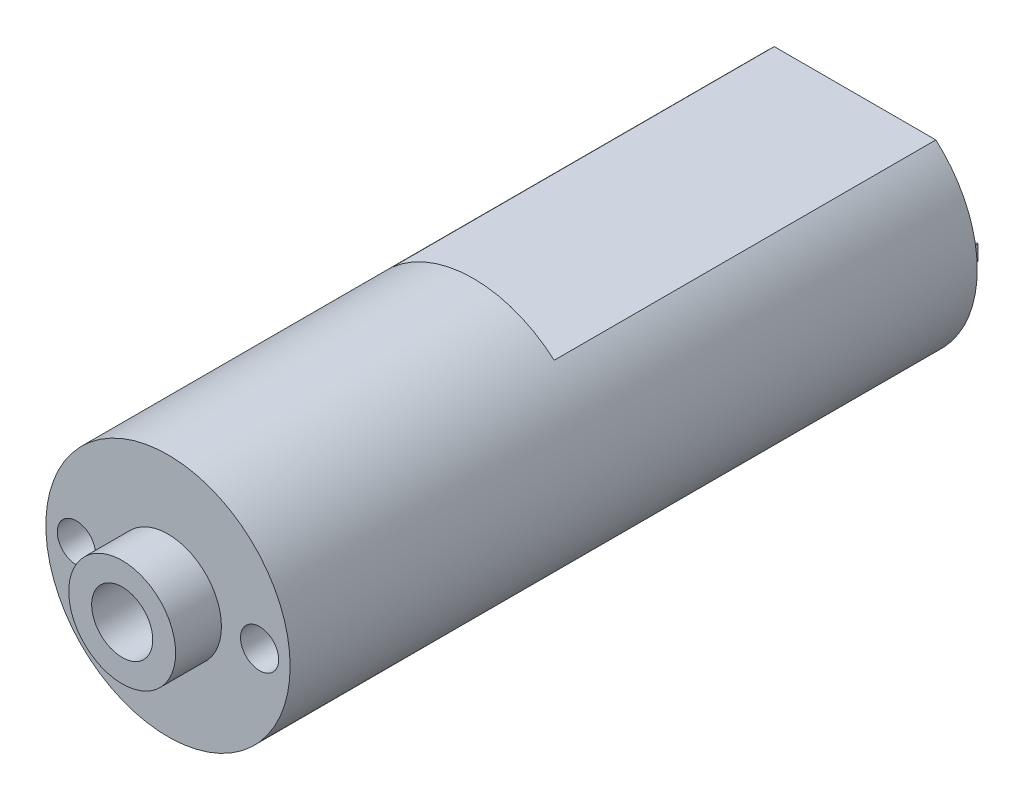
SolidWorks part; units mm, degrees
ref_plane "Ön Düzlem" through (0, 0, 0) normal (0, 0, 1) x (1, 0, 0)
ref_plane "Üst Düzlem" through (0, 0, 0) normal (0, 1, 0) x (1, 0, 0)
ref_plane "Sağ Düzlem" through (0, 0, 0) normal (1, 0, 0) x (0, 0, -1)
sketch "Sketch1" plane through (0, 0, 0) normal (0, 0, 1) x (1, 0, 0)
  line L0 (-6, 0) -> (6, 0) construction
  circle A0 centre (0, 0) radius 8
  circle A1 centre (0, 0) radius 2
  circle A2 centre (-6, 0) radius 1.25
  circle A3 centre (6, 0) radius 1.25
  circle A4 centre (0, 0) radius 3.5
  point P8 (0, 0)
  dimension "D1" = 16
  dimension "D2" = 4
  dimension "D4" = 2.5
  dimension "D5" = 7
  dimension "D3" = 12
extrude "Boss-Extrude1" add sketch "Sketch1" against normal blind 20 contours L0 A4 A1 | A4 L0 A1 | A0 A2 A4 A3 region at (0, 2.0783, 0) region at (2.75, -0.0783, 0) region at (-7.7737, 0, 0)
extrude "Boss-Extrude2" add sketch "Sketch1<3>" along normal blind 3 contours A4 L0 A1 | L0 A4 A1 region at (0, 2.0783, 0) region at (2.75, -0.0783, 0)
sketch "Sketch1<3>" plane through (0, 0, 0) normal (0, 0, 1) x (1, 0, 0) same geometry as "Sketch1"
sketch "Sketch2" plane through (0, 0, -20) normal (0, 0, -1) x (-1, 0, 0)
  line L0 (-5.2915, 6) -> (5.2915, 6)
  line L1 (-5.2915, -6) -> (5.2915, -6)
  line L2 (0, 6) -> (0, -6) construction
  circle A0 centre (0, 0) radius 8 construction
  arc A1 (-5.2915, 6) -> (-5.2915, -6) centre (0, 0) ccw
  arc A2 (5.2915, -6) -> (5.2915, 6) centre (0, 0) ccw
  point P9 (0, 0)
  dimension "D1" = 12
extrude "Boss-Extrude3" add sketch "Sketch2" along normal blind 25
sketch "Sketch3" plane through (0, 0, -45) normal (0, 0, -1) x (-1, 0, 0)
  line L0 (0, 0) -> (0, 2) construction
  line L5 (6.95, 0.5) -> (7.05, 0.5)
  line L6 (6.95, 0.5) -> (6.95, -0.5)
  line L7 (6.95, -0.5) -> (7.05, -0.5)
  line L8 (7.05, 0.5) -> (7.05, -0.5)
  line L9 (6.95, 0.5) -> (7.05, -0.5) construction
  line L10 (6.95, -0.5) -> (7.05, 0.5) construction
  line L11 (-6.95, -0.5) -> (-7.05, 0.5) construction
  line L12 (-6.95, 0.5) -> (-7.05, -0.5) construction
  line L13 (-7.05, 0.5) -> (-7.05, -0.5)
  line L14 (-6.95, -0.5) -> (-7.05, -0.5)
  line L15 (-6.95, 0.5) -> (-6.95, -0.5)
  line L16 (-6.95, 0.5) -> (-7.05, 0.5)
  circle A0 centre (0, 0) radius 2
  point P3 (7, 0)
  point P13 (-7, 0)
  dimension "D1" = 4
  dimension "D2" = 0.1
  dimension "D3" = 1
  dimension "D4" = 7
extrude "Boss-Extrude5" add sketch "Sketch3" along normal blind 1
fillet "Fillet2" radius 1 1 edges at (-2, 0, -46)
